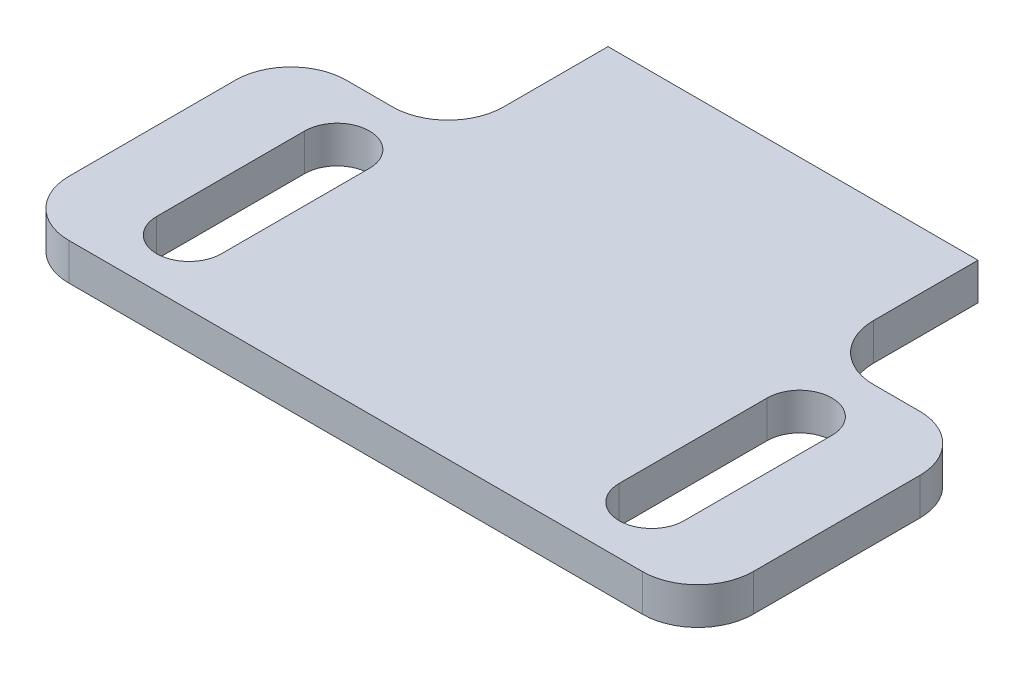
SolidWorks part; units mm, degrees
ref_plane "前视基准面" through (0, 0, 0) normal (0, 0, 1) x (1, 0, 0)
ref_plane "上视基准面" through (0, 0, 0) normal (0, 1, 0) x (1, 0, 0)
ref_plane "右视基准面" through (0, 0, 0) normal (1, 0, 0) x (0, 0, -1)
other "Configuration Table"
sketch "草图1" plane through (0, 0, 0) normal (0, 1, 0) x (1, 0, 0)
  line L0 (-10, 7.5) -> (-18.5, 7.5)
  line L1 (-18.5, -7.5) -> (18.5, -7.5)
  line L2 (-18.5, -7.5) -> (-18.5, 7.5)
  line L4 (18.5, -7.5) -> (18.5, 7.5)
  line L5 (-18.5, -7.5) -> (18.5, 7.5) construction
  line L6 (-18.5, 7.5) -> (18.5, -7.5) construction
  line L7 (10, 16.146) -> (-10, 16.146)
  line L8 (10, 16.146) -> (10, 7.5)
  line L10 (-10, 16.146) -> (-10, 7.5)
  line L11 (10, 16.146) -> (-10, 7.5) construction
  line L12 (10, 7.5) -> (-10, 16.146) construction
  line L13 (10, 7.5) -> (18.5, 7.5)
  point P0 (0, 0)
  point P6 (0, 11.823)
base flange "基体-法兰1" sketch "草图1" thickness 2 reverse thickness direction no parameters "D1"=10
fillet "圆角1" radius 3 6 edges at (18.5, -1, -7.5) (18.5, -1, 7.5) (-18.5, -1, 7.5) (-18.5, -1, -7.5) (10, -1, -7.5) (-10, -1, -7.5)
sketch "草图6" plane through (0, -2, 0) normal (0, -1, 0) x (1, 0, 0)
  line L0 (-12.5, 0) -> (12.5, 0)
  line L1 (12.5, 4) -> (12.5, -4) construction
  line L2 (-12.5, 4) -> (-12.5, -4) construction
  line L3 (-10.75, 4) -> (-10.75, -4)
  line L4 (-14.25, 4) -> (-14.25, -4)
  line L5 (14.25, 4) -> (14.25, -4)
  line L6 (10.75, 4) -> (10.75, -4)
  arc A0 (-10.75, 4) -> (-14.25, 4) centre (-12.5, 4) ccw
  arc A1 (-14.25, -4) -> (-10.75, -4) centre (-12.5, -4) ccw
  arc A2 (14.25, 4) -> (10.75, 4) centre (12.5, 4) ccw
  arc A3 (10.75, -4) -> (14.25, -4) centre (12.5, -4) ccw
  point P4 (0, 0)
  point P7 (-12.5, 0)
  point P12 (12.5, 0)
extrude "切除-拉伸1" cut sketch "草图6" against normal blind 10
sketch "折弯-线1" plane through (0, 0, 0) normal (0, 1, 0) x (1, 0, 0)
sketch "边界框1" plane through (0, 0, 0) normal (0, 1, 0) x (1, 0, 0)
sheet metal parameters "钣金6" thickness 2 parameters "D1"=10
flat pattern "平板型式6" [suppressed]
sketch "折弯-线2" plane through (0, 0, 0) normal (0, 1, 0) x (1, 0, 0)
sketch "边界框2" [suppressed] plane through (0, 0, 0) normal (0, 1, 0) x (1, 0, 0)
sheet metal parameters "钣金7" thickness 2 parameters "D1"=10
flat pattern "平板型式6"
sketch "折弯-线2" plane through (0, 0, 0) normal (0, 1, 0) x (1, 0, 0)
sketch "边界框2" [suppressed] plane through (0, 0, 0) normal (0, 1, 0) x (1, 0, 0)
